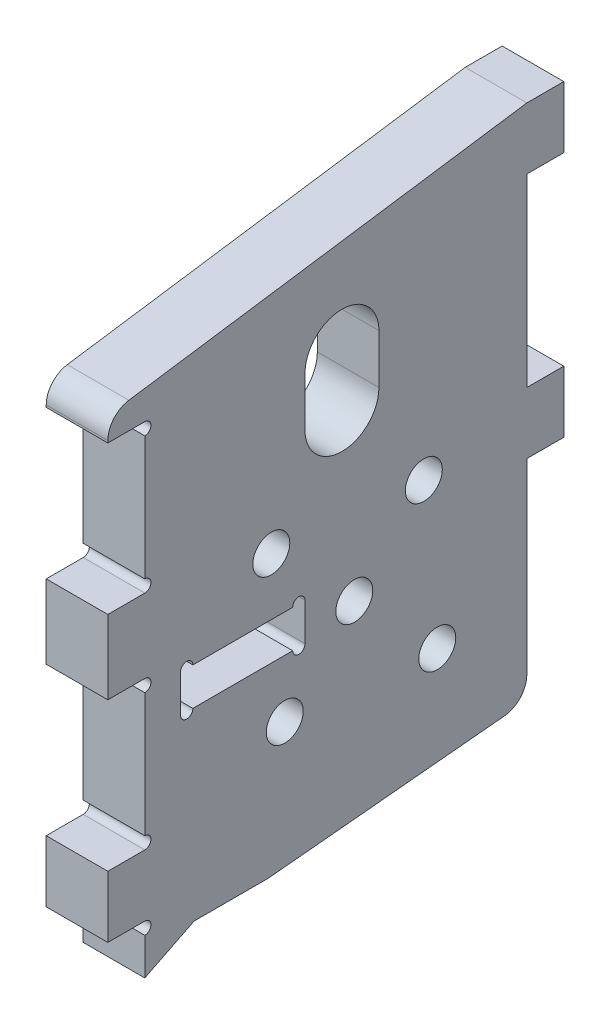
SolidWorks part; units mm, degrees
ref_plane "Front Plane" through (0, 0, 0) normal (0, 0, 1) x (1, 0, 0)
ref_plane "Top Plane" through (0, 0, 0) normal (0, 1, 0) x (1, 0, 0)
ref_plane "Right Plane" through (0, 0, 0) normal (1, 0, 0) x (0, 0, -1)
sketch "Sketch1" plane through (0, 0, 0) normal (1, 0, 0) x (0, 0, -1)
  line L0 (17, 28) -> (17, 23)
  line L1 (17, 28) -> (14, 28)
  line L2 (14, 28) -> (-20, 23)
  line L3 (-20, 23) -> (-20, -14)
  line L4 (14, -14) -> (-20, -14)
  line L6 (17, 23) -> (14, 23)
  line L7 (14, 23) -> (14, 8)
  line L8 (14, 8) -> (17, 8)
  line L9 (17, 8) -> (17, 3)
  line L10 (17, 3) -> (14, 3)
  line L11 (-6.7339, 6.7011) -> (6.7339, -6.7011) construction
  line L12 (20, 36.7745) -> (20, -39.1651) construction
  line L13 (5.643, 5.6706) -> (-5.643, -5.6706) construction
  line L14 (14, 3) -> (14, -14)
  circle A0 centre (0, 0) radius 18 construction
  circle A1 centre (-6.7339, 6.7011) radius 1.5
  circle A2 centre (-5.643, -5.6706) radius 1.5
  circle A3 centre (6.7339, -6.7011) radius 1.5
  circle A4 centre (5.643, 5.6706) radius 1.5
  circle A5 centre (0, 0) radius 1.5
  dimension "D2" = 36
  dimension "D4" = 3
  dimension "D1" = 20
  dimension "D3" = 13.4022
  dimension "D5" = 5
  dimension "D6" = 3
  dimension "D7" = 17
  dimension "D8" = 14
  dimension "D9" = 17
  dimension "D10" = 28
  dimension "D11" = 20
  dimension "D12" = 5
  dimension "D13" = 5.643
  dimension "D14" = 6.7339
extrude "Boss-Extrude1" add sketch "Sketch1" along normal blind 5
sketch "Sketch2" plane through (5, 0, 0) normal (1, 0, 0) x (0, 0, -1)
  line L0 (-20, 21.1) -> (-17, 21.1)
  line L1 (-14.1, 2.05) -> (-4, 2.05)
  line L2 (-14.1, 2.05) -> (-14.1, -1)
  line L3 (-14.1, -1) -> (-4, -1)
  line L4 (-4, 2.05) -> (-4, -1)
  line L5 (-20, -14) -> (14, -14) construction
  line L7 (-20, 23) -> (-20, -14) construction
  line L8 (-17, 21.1) -> (-17, 9.05)
  line L9 (-17, -9) -> (-20, -9)
  line L10 (-17, 9.05) -> (-20, 9.05)
  line L11 (-17, -9) -> (-17, 3.05)
  line L12 (-17, 3.05) -> (-20, 3.05)
  line L13 (-20, 21.1) -> (-20, 9.05)
  line L14 (-20, 3.05) -> (-20, -9)
  dimension "D3" = 10.1
  dimension "D1" = 3.05
  dimension "D2" = 13
  dimension "D4" = 4
  dimension "D5" = 3
  dimension "D6" = 12.05
  dimension "D7" = 12.05
  dimension "D8" = 6
  dimension "D9" = 5
extrude "Cut-Extrude1" cut sketch "Sketch2" against normal through all
sketch "Sketch4" plane through (5, 0, 0) normal (1, 0, 0) x (0, 0, -1)
  line L0 (-4, 18) -> (-4, 14)
  line L1 (2, 18) -> (2, 14)
  line L4 (14, 8) -> (14, 23) construction
  arc A0 (-4, 18) -> (2, 18) centre (-1, 18) cw
  arc A1 (-4, 14) -> (2, 14) centre (-1, 14) ccw
  dimension "D1" = 4
  dimension "D4" = 15
  dimension "D2" = 3
  dimension "D3" = 14
extrude "Cut-Extrude3" cut sketch "Sketch4" against normal blind 10
sketch "Sketch5" plane through (5, 0, 0) normal (1, 0, 0) x (0, 0, -1)
  line L0 (14, -14) -> (-7, -16)
  line L1 (-7, -16) -> (-13, -16)
  line L2 (-13, -16) -> (-17, -18)
  line L3 (-17, -18) -> (-17, -14)
  line L4 (-20, -14) -> (14, -14) construction
  line L5 (-17, -9) -> (-17, 3.05) construction
  line M7 (-20, -14) -> (14, -14)
  dimension "D1" = 2
  dimension "D2" = 4
  dimension "D3" = 4
  dimension "D4" = 6
extrude "Boss-Extrude3" add sketch "Sketch5" against normal blind 5 contours L3 L2 L1 L0 M7 region at (5, -14.9926, 6.7259)
fillet "Fillet1" radius 2 2 edges at (2.5, 23, 20) (2.5, -14, -14)
sketch "Sketch6" plane through (5, 0, 0) normal (1, 0, 0) x (0, 0, -1)
  line L0 (-17, 9.05) -> (-17, 21.1) construction
  line L1 (-17, 21.1) -> (-17, 20.1)
  line L2 (-17, 10.05) -> (-17, 9.05)
  line L3 (-17, -8) -> (-17, -9)
  line L4 (-17, 3.05) -> (-17, 2.05)
  line L5 (-4, 2.05) -> (-14.1, 2.05) construction
  line L6 (-14.1, -1) -> (-4, -1) construction
  line L7 (-14.1, 2.05) -> (-13.1, 2.05)
  line L8 (-13.1, -1) -> (-14.1, -1)
  line L9 (-5, 2.05) -> (-4, 2.05)
  line L11 (-4, -1) -> (-5, -1)
  line L13 (-17, -14) -> (-17, -15)
  arc A0 (-17, 21.1) -> (-17, 20.1) centre (-17, 20.6) cw
  arc A1 (-17, 10.05) -> (-17, 9.05) centre (-17, 9.55) cw
  arc A2 (-17, -8) -> (-17, -9) centre (-17, -8.5) cw
  arc A3 (-17, 3.05) -> (-17, 2.05) centre (-17, 2.55) cw
  arc A4 (-14.1, 2.05) -> (-13.1, 2.05) centre (-13.6, 2.05) cw
  arc A5 (-14.1, -1) -> (-13.1, -1) centre (-13.6, -1) ccw
  arc A6 (-5, 2.05) -> (-4, 2.05) centre (-4.5, 2.05) cw
  arc A7 (-5, -1) -> (-4, -1) centre (-4.5, -1) ccw
  arc A8 (-17, -14) -> (-17, -15) centre (-17, -14.5) cw
  dimension "D1" = 0.5
  dimension "D2" = 0.5
  dimension "D3" = 0.5
  dimension "D4" = 0.5
  dimension "D5" = 0.5
  dimension "D6" = 0.5
  dimension "D7" = 0.5
  dimension "D8" = 0.5
  dimension "D9" = 0.5
extrude "Cut-Extrude4" cut sketch "Sketch6" against normal blind 5
